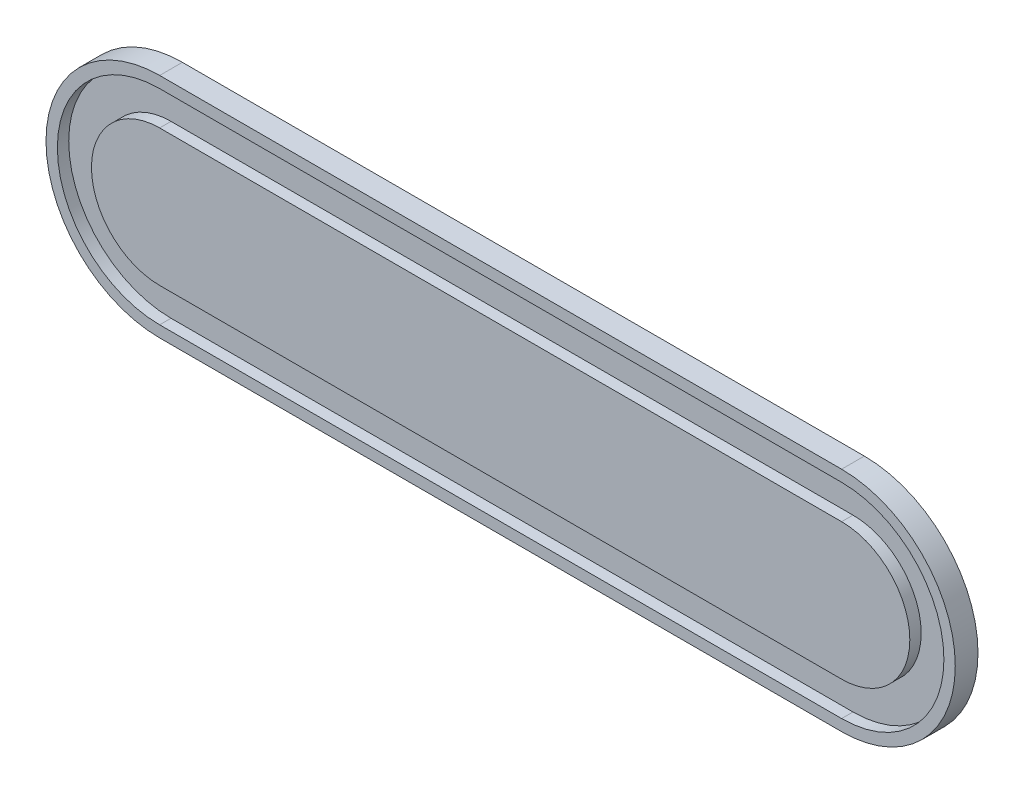
SolidWorks part; units mm, degrees
material "ﾊﾞﾙｻ"
ref_plane "正面" through (0, 0, 0) normal (0, 0, 1) x (1, 0, 0)
ref_plane "平面" through (0, 0, 0) normal (0, 1, 0) x (1, 0, 0)
ref_plane "右側面" through (0, 0, 0) normal (1, 0, 0) x (0, 0, -1)
sketch "ｽｹｯﾁ1" plane through (0, 0, 0) normal (0, 0, 1) x (1, 0, 0)
  line L0 (1.5666, 0) -> (60001.5666, 0) construction
  line L1 (1.5666, 10000) -> (60001.5666, 10000)
  line L2 (1.5666, -10000) -> (60001.5666, -10000)
  line L3 (1.5666, 0) -> (60001.5666, 0) construction
  line L4 (1.5666, 9000) -> (60001.5666, 9000)
  line L5 (1.5666, -9000) -> (60001.5666, -9000)
  line L6 (1.5666, 0) -> (60001.5666, 0) construction
  line L7 (1.5666, 6000) -> (60001.5666, 6000)
  line L8 (1.5666, -6000) -> (60001.5666, -6000)
  arc A0 (1.5666, 10000) -> (1.5666, -10000) centre (1.5666, 0) ccw
  arc A1 (60001.5666, -10000) -> (60001.5666, 10000) centre (60001.5666, 0) ccw
  arc A2 (1.5666, 9000) -> (1.5666, -9000) centre (1.5666, 0) ccw
  arc A3 (60001.5666, -9000) -> (60001.5666, 9000) centre (60001.5666, 0) ccw
  arc A4 (1.5666, 6000) -> (1.5666, -6000) centre (1.5666, 0) ccw
  arc A5 (60001.5666, -6000) -> (60001.5666, 6000) centre (60001.5666, 0) ccw
  point P3 (30001.5666, 0)
  point P10 (30001.5666, 0)
  point P17 (30001.5666, 0)
extrude "ﾎﾞｽ - 押し出し1" add sketch "ｽｹｯﾁ1" along normal blind 1000 contours L2 A1 L1 A0 A3 L5 A2 L4 | L8 A5 L7 A4 region at (30001.5666, 9175.3789, 0) region at (30001.5666, 0, 0)
extrude "ﾎﾞｽ - 押し出し2" add sketch "ｽｹｯﾁ1<3>" against normal blind 1000 contours L2 A1 L1 A0 A3 L5 A2 L4 | L5 A3 L4 A2 A5 L8 A4 L7 | L8 A5 L7 A4 region at (30001.5666, 9175.3789, 0) region at (30001.5666, 8199.5002, 0) region at (30001.5666, 0, 0)
sketch "ｽｹｯﾁ1<3>" plane through (0, 0, 0) normal (0, 0, 1) x (1, 0, 0) same geometry as "ｽｹｯﾁ1"
